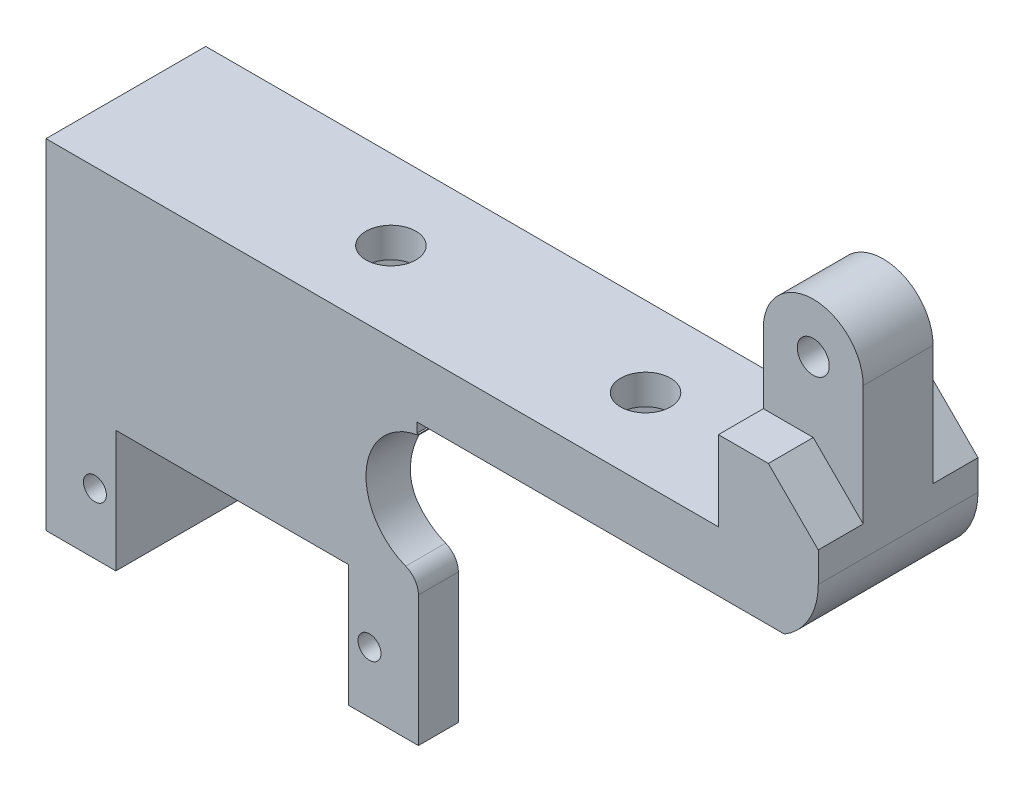
SolidWorks part; units mm, degrees
ref_plane "Plan de face" through (0, 0, 0) normal (0, 0, 1) x (1, 0, 0)
ref_plane "Plan de dessus" through (0, 0, 0) normal (0, 1, 0) x (1, 0, 0)
ref_plane "Plan de droite" through (0, 0, 0) normal (1, 0, 0) x (0, 0, -1)
sketch "Esquisse1" plane through (0, 0, 0) normal (0, 0, 1) x (1, 0, 0)
  line L0 (0, 0) -> (67.35, 0)
  line L1 (67.35, 0) -> (67.35, 20)
  line L2 (67.35, 20) -> (77.35, 20)
  line L3 (0, 0) -> (0, -34)
  line L4 (0, -34) -> (7, -34)
  line L5 (7, -34) -> (7, -7)
  line L6 (7, -7) -> (30.3, -7)
  line L7 (30.3, -7) -> (30.3, -34)
  line L8 (30.3, -34) -> (37.3, -34)
  line L9 (37.3, -34) -> (37.3, -7)
  line L10 (37.3, -7) -> (77.35, -7)
  line L11 (77.35, -7) -> (77.35, 20)
  line L12 (4.9, -27.9) -> (32.4, -27.9) construction
  line L13 (18.65, -27.9) -> (18.65, -7) construction
  circle A0 centre (4.9, -27.9) radius 1.15
  circle A1 centre (32.4, -27.9) radius 1.15
  dimension "D8" = 2.3
  dimension "D1" = 27
  dimension "D2" = 7
  dimension "D3" = 7
  dimension "D4" = 23.3
  dimension "D5" = 40.05
  dimension "D6" = 10
  dimension "D7" = 20
  dimension "D9" = 6.1
  dimension "D10" = 27.5
extrude "Boss.-Extru.1" add sketch "Esquisse1" along normal blind 16
sketch "Esquisse5" plane through (0, 20, 0) normal (0, 1, 0) x (1, 0, 0)
  line L0 (67.35, -16) -> (67.35, 0) construction
  line L1 (77.35, 0) -> (67.35, 0)
  line L2 (77.35, 0) -> (77.35, -4.5)
  line L3 (77.35, -4.5) -> (67.35, -4.5)
  line L4 (67.35, 0) -> (67.35, -4.5)
  line L6 (77.35, -16) -> (67.35, -16)
  line L7 (77.35, -16) -> (77.35, -11.5)
  line L8 (77.35, -11.5) -> (67.35, -11.5)
  line L9 (67.35, -16) -> (67.35, -11.5)
  dimension "D1" = 7
extrude "Enlèv. mat.-Extru.3" cut sketch "Esquisse5" against normal blind 12
sketch "Esquisse6" plane through (0, 0, 11.5) normal (0, 0, 1) x (1, 0, 0)
  line L0 (67.35, 15) -> (65.3495, 15)
  line L1 (65.3495, 15) -> (65.3495, 22.0005)
  line L2 (65.3495, 22.0005) -> (79.3505, 22.0005)
  line L4 (67.35, 8) -> (67.35, 20) construction
  line L5 (77.35, 8) -> (77.35, 20) construction
  line L6 (77.35, 20) -> (67.35, 20) construction
  line L7 (77.35, 15) -> (79.3505, 15)
  line L8 (79.3505, 15) -> (79.3505, 22.0005)
  line L9 (72.35, 20) -> (72.35, 22.0005) construction
  circle A0 centre (72.35, 15) radius 1.6
  circle A1 centre (72.35, 15) radius 5 construction
  arc A2 (67.35, 15) -> (77.35, 15) centre (72.35, 15) cw
  dimension "D1" = 3.2
  dimension "D2" = 2.0005
extrude "Enlèv. mat.-Extru.4" cut sketch "Esquisse6" against normal through all contours L2 L8 L7 A2 L0 L1 | A0
sketch "Esquisse12" plane through (0, -34, 0) normal (0, -1, 0) x (-1, 0, 0)
  line L1 (-30.3, 0) -> (-37.3, 0)
  line L2 (-30.3, 0) -> (-30.3, -12)
  line L3 (-30.3, -12) -> (-37.3, -12)
  line L4 (-37.3, 0) -> (-37.3, -12)
  line L6 (-37.3, -16) -> (-37.3, 0) construction
  line L7 (-30.3, -16) -> (-37.3, -16) construction
  dimension "D1" = 4
extrude "Enlèv. mat.-Extru.7" cut sketch "Esquisse12" against normal up to surface (27 mm away) up to face at (18.65, -7, 8)
sketch "Esquisse14" plane through (0, 0, 16) normal (0, 0, 1) x (1, 0, 0)
  line L0 (30.3, -7) -> (30.3, -34) construction
  line L1 (7, -7) -> (30.3, -7)
  line L2 (7, -7) -> (7, -21.8)
  line L3 (7, -21.8) -> (30.3, -21.8)
  line L4 (30.3, -7) -> (30.3, -21.8)
  line L5 (32.4, -34) -> (32.4, -21.8) construction
  line L6 (30.3, -34) -> (37.3, -34) construction
  line L7 (32.4, -21.8) -> (30.3, -21.8) construction
  circle A0 centre (32.4, -27.9) radius 1.15 construction
  point P11 (32.4, -27.9)
extrude "Boss.-Extru.2" add sketch "Esquisse14" against normal up to surface (4 mm away) up to face at (33.55, -27.9, 12)
fillet "Congé1" radius 10 2 edges at (22.15, -7, 12) (7, -7, 6)
sketch "Esquisse15" plane through (0, 0, 16) normal (0, 0, 1) x (1, 0, 0)
  line L0 (37.3, -7) -> (77.35, -7) construction
  line L1 (37.3, -34) -> (37.3, -7) construction
  circle A0 centre (38.3, -13.25) radius 6.25
  dimension "D1" = 12.5
  dimension "D2" = 1
extrude "Enlèv. mat.-Extru.8" cut sketch "Esquisse15" against normal blind 18
fillet "Congé2" radius 2 1 edges at (37.3, -19.4195, 14)
fillet "Congé3" radius 7 1 edges at (77.35, -7, 8)
ref_plane "Plan1" through (0, 0, 8) normal (0, 0, -1) x (-1, 0, 0)
sketch "Esquisse16" plane through (0, 0, 8) normal (0, 0, -1) x (-1, 0, 0)
  line L0 (-52.05, 0) -> (-52.05, -7)
  line L1 (-52.05, -7) -> (-48.05, -7) construction
  line L2 (-48.05, -7) -> (-49.55, -5.5)
  line L3 (-49.55, -5.5) -> (-49.55, 0)
  line L4 (-49.55, 0) -> (-52.05, 0)
  line L5 (-17, -7) -> (-70.35, -7) construction
  line L6 (-67.35, 0) -> (0, 0) construction
  line L8 (-48.05, -7) -> (-52.05, -7) construction
  line L9 (-48.05, -7) -> (-48.05, -57)
  line L10 (-48.05, -57) -> (-52.05, -57)
  line L11 (-52.05, -7) -> (-52.05, -57)
  dimension "D1" = 25.3
  dimension "D2" = 2.5
  dimension "D3" = 1.5
  dimension "D4" = 1.5
  dimension "D5" = 50
revolve "Enlèvement de matière-Révolution1" cut sketch "Esquisse16" angle 360 about L0
pattern_linear "Répétition linéaire1" count 2 spacing 25.5 along (-1, 0, 0) of "Enlèvement de matière-Révolution1"
sketch "Esquisse17" plane through (77.35, 0, 0) normal (1, 0, 0) x (0, 0, -1)
  line L0 (-9, -7) -> (-16, -6)
  line L1 (-16, -6) -> (-16, -7)
  line L2 (-16, -7) -> (-9, -7)
  dimension "D1" = 1
  dimension "D2" = 7
extrude "Enlèv. mat.-Extru.9" cut sketch "Esquisse17" against normal blind 40.2137
sketch "Esquisse18" plane through (0, -7, 0) normal (0, -1, 0) x (1, 0, 0)
  line L0 (56.2, 10.396) -> (56.2, 5.604)
  line L1 (56.2, 5.604) -> (52.05, 3.208)
  line L2 (52.05, 3.208) -> (47.9, 5.604)
  line L3 (47.9, 5.604) -> (47.9, 10.396)
  line L4 (47.9, 10.396) -> (52.05, 12.792)
  line L5 (52.05, 12.792) -> (56.2, 10.396)
  circle A0 centre (52.05, 8) radius 4.792 construction
  dimension "D1" = 8.3
extrude "Enlèv. mat.-Extru.10" cut sketch "Esquisse18" against normal blind 4 and the other way through all
pattern_linear "Répétition linéaire2" count 2 spacing 25.5 along (-1, 0, 0) of "Enlèv. mat.-Extru.10"
chamfer "Chamfer1" distance 5 angle 45 2 edges at (77.35, 8, 13.75) (77.35, 8, 2.25)
